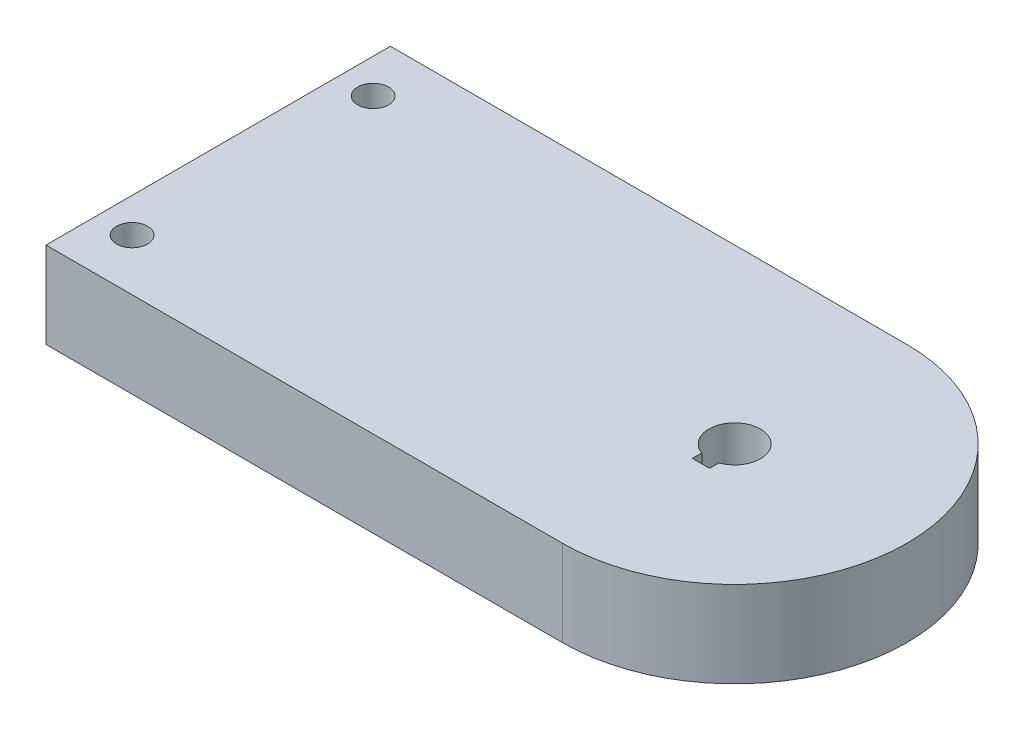
SolidWorks part; units mm, degrees
material "3.1325 (EN-AW 2017A)"
ref_plane "Płaszczyzna przednia" through (0, 0, 0) normal (0, 0, 1) x (1, 0, 0)
ref_plane "Płaszczyzna górna" through (0, 0, 0) normal (0, 1, 0) x (1, 0, 0)
ref_plane "Płaszczyzna prawa" through (0, 0, 0) normal (1, 0, 0) x (0, 0, -1)
sketch "Szkic1" plane through (0, 0, 0) normal (0, 1, 0) x (1, 0, 0)
  line L0 (0, 0) -> (300, 0) construction
  line L1 (0, -50) -> (0, 50)
  line L2 (0, 50) -> (150, 50)
  line L4 (0, -50) -> (150, -50)
  line L5 (150, 0) -> (150, -9.9985) construction
  line L6 (147.5, -9.8) -> (152.5, -9.8)
  line L7 (152.5, -9.8) -> (152.5, -7.0711)
  line L8 (147.5, -9.8) -> (147.5, -7.0711)
  arc A0 (152.5, -7.0711) -> (147.5, -7.0711) centre (150, 0) ccw
  arc A1 (150, -50) -> (150, 50) centre (150, 0) ccw
  point P15 (150, -9.8)
  dimension "D3" = 5
  dimension "D2" = 50
  dimension "D1" = 7.5
  dimension "D4" = 150
  dimension "D5" = 9.8
extrude "Dodanie-wyciągnięcie1" add sketch "Szkic1" along normal blind 25
sketch "Szkic2" plane through (0, 0, 0) normal (0, -1, 0) x (1, 0, 0)
  line L1 (0, 50) -> (150, 50) construction
  line L2 (150, -50) -> (0, -50) construction
  line L3 (10, 50) -> (10, -50) construction
  line L4 (0, -50) -> (0, 50) construction
  line L5 (0, 0) -> (150, 0) construction
  point P13 (10, 35)
  point P14 (10, -35)
  dimension "D1" = 10
  dimension "D2" = 70
  dimension "D3" = 140
hole_wizard "Pogłębienie walcowe pod M8 Wkręt z łbem walcowym z gniazdem sześciokątnym1" positions "Szkic 3D1" profile "Szkic3" counterbore size "M8" standard "ISO"
sketch3d "Szkic 3D1"
  point P0 (10, 0, 35)
  point P3 (10, 0, -35)
sketch "Szkic3" plane through (10, 0, 35) normal (1, 0, 0) x (0, 0, -1)
  line L0 (0, 0) -> (0, 28.9539)
  line L1 (0, 28.9539) -> (4.5, 26.25)
  line L2 (4.5, 26.25) -> (4.5, 8.6)
  line L3 (4.5, 8.6) -> (7.5, 8.6)
  line L4 (7.5, 8.6) -> (7.5, 0)
  line L5 (7.5, 0) -> (0, 0)
  line L10 (0, 28.9539) -> (-4.5, 26.25) construction
  line L11 (0, -6.35) -> (0, 107.95) construction
  dimension "Średnica otworu" = 9
  dimension "Głębokość otworu" = 26.25
  dimension "Średnica pogłębienia walcowego" = 15
  dimension "Głębokość pogłębienia walcowego" = 8.6
  dimension "Kąt wiertła" = 118
sketch "Szkic4" plane through (0, 0, 0) normal (0, -1, 0) x (1, 0, 0)
  line L0 (0, 0) -> (142.5, 0) construction
  line L1 (31.2133, 33.297) -> (66.9685, 4.6847)
  line L2 (41.3412, -43) -> (112.3066, -43)
  line L4 (130.5586, -29.3931) -> (130.5586, 29.3931)
  line L5 (41.3412, 43) -> (112.3066, 43)
  line L6 (23.0893, -43) -> (130.5586, 43) construction
  line L7 (130.5586, -43) -> (23.0893, 43) construction
  line L8 (0, 50) -> (150, 50) construction
  line L9 (76.8239, 50) -> (76.8239, -50) construction
  line L10 (150, -50) -> (0, -50) construction
  line L11 (86.6794, 4.6847) -> (122.4346, 33.297)
  line L12 (38.2172, 34.0961) -> (70.5759, 8.2018)
  line L13 (38.2172, -34.0961) -> (70.5759, -8.2018)
  line L14 (31.2133, -33.297) -> (66.9685, -4.6847)
  line L15 (83.072, -8.2018) -> (115.4307, -34.0961)
  line L16 (86.6794, -4.6847) -> (122.4346, -33.297)
  line L17 (83.072, 8.2018) -> (115.4307, 34.0961)
  line L18 (23.0893, -29.3931) -> (23.0893, 29.3931)
  arc A0 (31.2133, 33.297) -> (23.0893, 29.3931) centre (28.0893, 29.3931) ccw
  arc A1 (147.5, 7.0711) -> (152.5, 7.0711) centre (150, 0) ccw construction
  arc A2 (70.5759, 8.2018) -> (83.072, 8.2018) centre (76.8239, 16.0096) ccw
  arc A3 (41.3412, 43) -> (38.2172, 34.0961) centre (41.3412, 38) ccw
  arc A4 (41.3412, -43) -> (38.2172, -34.0961) centre (41.3412, -38) cw
  arc A5 (112.3066, -43) -> (115.4307, -34.0961) centre (112.3066, -38) ccw
  arc A6 (112.3066, 43) -> (115.4307, 34.0961) centre (112.3066, 38) cw
  arc A7 (31.2133, -33.297) -> (23.0893, -29.3931) centre (28.0893, -29.3931) cw
  arc A8 (122.4346, -33.297) -> (130.5586, -29.3931) centre (125.5586, -29.3931) ccw
  arc A9 (122.4346, 33.297) -> (130.5586, 29.3931) centre (125.5586, 29.3931) cw
  arc A10 (70.5759, -8.2018) -> (83.072, -8.2018) centre (76.8239, -16.0096) cw
  arc A11 (66.9685, -4.6847) -> (66.9685, 4.6847) centre (63.2197, 0) ccw
  arc A12 (86.6794, -4.6847) -> (86.6794, 4.6847) centre (90.4282, 0) cw
  point P8 (76.8239, 0)
  dimension "D2" = 10
  dimension "D4" = 6
  dimension "D5" = 126.9107
  dimension "D3" = 10
  dimension "D1" = 7
  dimension "D6" = 19.4414
  dimension "D7" = 3.124
  dimension "D8" = 7.004
extrude "Wytnij-wyciągnięcie1" cut sketch "Szkic4" against normal blind 15
ref_axis "Oś1" through (150, 25, 0) along (0, -1, 0)
ref_point "Punkt1"
